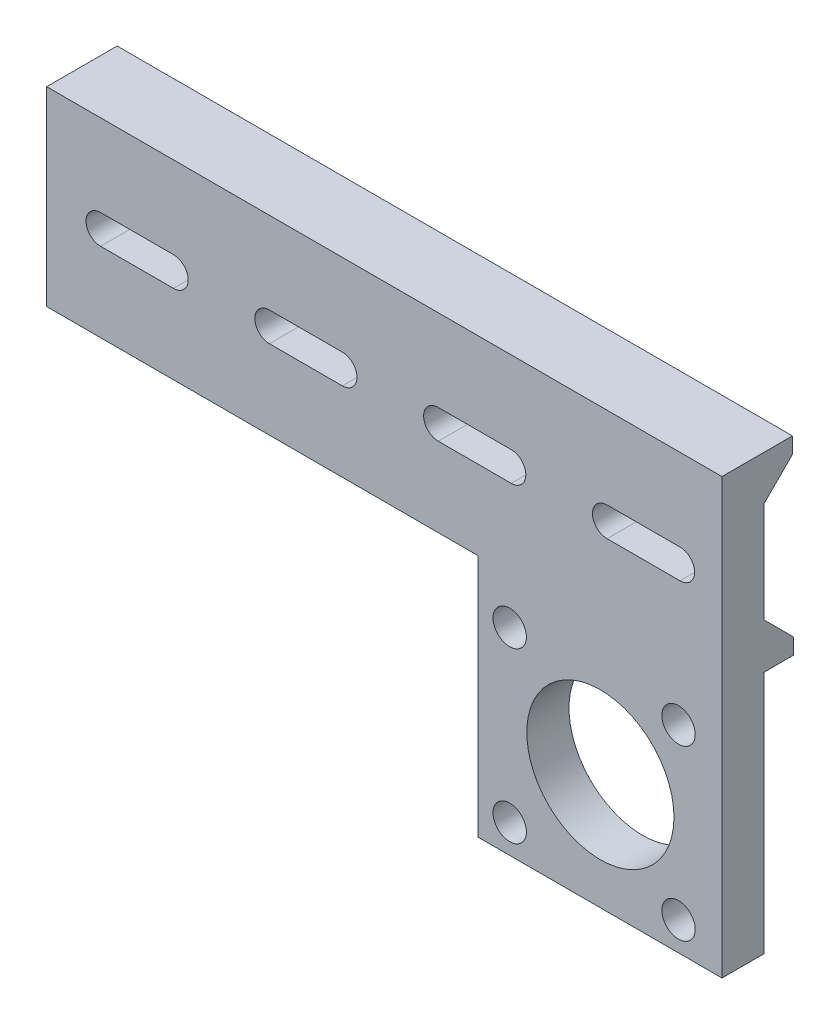
SolidWorks part; units mm, degrees
ref_plane "Front Plane" through (0, 0, 0) normal (0, 0, 1) x (1, 0, 0)
ref_plane "Top Plane" through (0, 0, 0) normal (0, 1, 0) x (1, 0, 0)
ref_plane "Right Plane" through (0, 0, 0) normal (1, 0, 0) x (0, 0, -1)
sketch "Sketch2" plane through (0, 0, 40) normal (0, 0, 1) x (1, 0, 0)
  line L1 (-58.4044, 35.4344) -> (-0.5627, 35.4344)
  line L2 (-58.4044, 35.4344) -> (-58.4044, -22.3289)
  line L3 (-58.4044, -22.3289) -> (-0.5627, -22.3289)
  line L4 (-0.5627, 35.4344) -> (-0.5627, -22.3289)
extrude "Boss-Extrude2" add sketch "Sketch2" along normal blind 10
sketch "Sketch3" plane through (0, 0, 50) normal (0, 0, 1) x (1, 0, 0)
  circle A0 centre (-29.3755, 4.9656) radius 17.4379
extrude "Cut-Extrude1" cut sketch "Sketch3" against normal blind 10
sketch "Sketch4" plane through (0, 0, 50) normal (0, 0, 1) x (1, 0, 0)
  circle A0 centre (-50.8631, -15.5453) radius 3.9557
extrude "Cut-Extrude2" cut sketch "Sketch4" against normal blind 10
pattern_linear "LPattern1" count 2 spacing 40 along (0, 1, 0) count 2 spacing 40 along (1, 0, 0) of "Cut-Extrude2"
sketch "Sketch6" plane through (-0.5627, 0, 0) normal (1, 0, 0) x (0, 0, -1)
  line L0 (-50, 35.4344) -> (-33.1047, 35.4344)
  line L1 (-33.1047, 35.4344) -> (-33.1047, 39.2329)
  line L2 (-33.1047, 39.2329) -> (-40, 46.1282)
  line L3 (-40, 46.1282) -> (-40, 70.0722)
  line L4 (-40, 70.0722) -> (-33.3087, 76.7636)
  line L5 (-33.3087, 76.7636) -> (-33.3087, 80.5621)
  line L6 (-33.3087, 80.5621) -> (-50, 80.5621)
  line L7 (-50, 80.5621) -> (-50, 35.4344)
  dimension "D1" = 10
extrude "Boss-Extrude3" add sketch "Sketch6" against normal blind 160
sketch "Sketch7" plane through (0, 0, 50) normal (0, 0, 1) x (1, 0, 0)
  line L0 (-147.7937, 57.6608) -> (-130.5058, 57.6608) construction
  line L1 (-147.7937, 61.1224) -> (-130.5058, 61.1224)
  line L2 (-147.7937, 54.1992) -> (-130.5058, 54.1992)
  arc A0 (-147.7937, 61.1224) -> (-147.7937, 54.1992) centre (-147.7937, 57.6608) ccw
  arc A1 (-130.5058, 54.1992) -> (-130.5058, 61.1224) centre (-130.5058, 57.6608) ccw
  point P2 (-139.1497, 57.6608)
extrude "Cut-Extrude4" cut sketch "Sketch7" against normal blind 140
pattern_linear "LPattern3" count 4 spacing 40 along (1, 0, 0) of "Cut-Extrude4"
